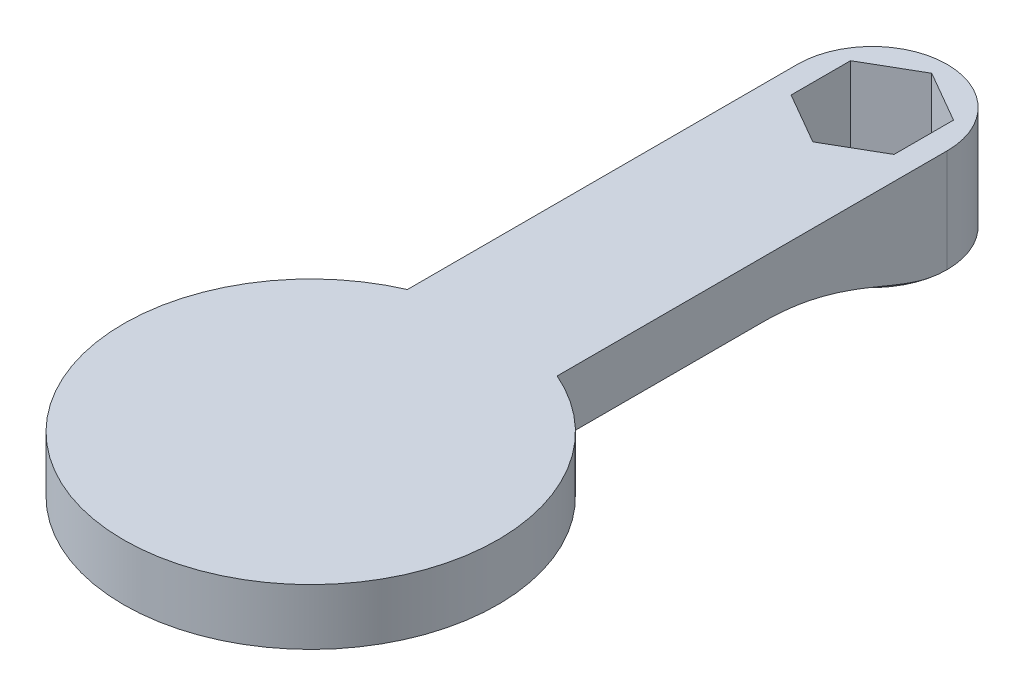
SolidWorks part; units mm, degrees
ref_plane "前视基准面" through (0, 0, 0) normal (0, 0, 1) x (1, 0, 0)
ref_plane "上视基准面" through (0, 0, 0) normal (0, 1, 0) x (1, 0, 0)
ref_plane "右视基准面" through (0, 0, 0) normal (1, 0, 0) x (0, 0, -1)
other "Configuration Table"
sketch "草图1" plane through (0, 0, 0) normal (0, 1, 0) x (1, 0, 0)
  line L1 (0, 3.1754) -> (-2.75, 1.5877)
  line L2 (-2.75, 1.5877) -> (-2.75, -1.5877)
  line L3 (-2.75, -1.5877) -> (0, -3.1754)
  line L4 (0, -3.1754) -> (2.75, -1.5877)
  line L5 (2.75, -1.5877) -> (2.75, 1.5877)
  line L6 (2.75, 1.5877) -> (0, 3.1754)
  circle A0 centre (0, 0) radius 2.75 construction
  circle A1 centre (0, 0) radius 4
  dimension "D1" = 5.5
  dimension "D2" = 8
extrude "凸台-拉伸1" add sketch "草图1" along normal blind 2.5
sketch "草图2" plane through (0, 2.5, 0) normal (0, 1, 0) x (1, 0, 0)
  line L0 (4, 0) -> (4, -20.8348)
  line L1 (-4, -20.8348) -> (-4, 0)
  line L8 (0, 3.1754) -> (-2.75, 1.5877)
  line L9 (2.75, 1.5877) -> (0, 3.1754)
  line L10 (2.75, -1.5877) -> (2.75, 1.5877)
  line L11 (0, -3.1754) -> (2.75, -1.5877)
  line L12 (-2.75, -1.5877) -> (0, -3.1754)
  line L13 (-2.75, 1.5877) -> (-2.75, -1.5877)
  line L14 (0, 3.1754) -> (-2.75, 1.5877)
  line L15 (2.75, 1.5877) -> (0, 3.1754)
  line L16 (2.75, -1.5877) -> (2.75, 1.5877)
  line L17 (0, -3.1754) -> (2.75, -1.5877)
  line L18 (-2.75, -1.5877) -> (0, -3.1754)
  line L19 (-2.75, 1.5877) -> (-2.75, -1.5877)
  arc A1 (4, 0) -> (-4, 0) centre (0, 0) ccw
  arc A2 (-4, -20.8348) -> (4, -20.8348) centre (0, -30) ccw
  dimension "D2" = 20
  dimension "D3" = 8
  dimension "D1" = 30
  dimension "D4" = 0
extrude "凸台-拉伸2" add sketch "草图2" along normal blind 3
fillet "圆角1" radius 10 1 edges at (0, 2.5, 4)
